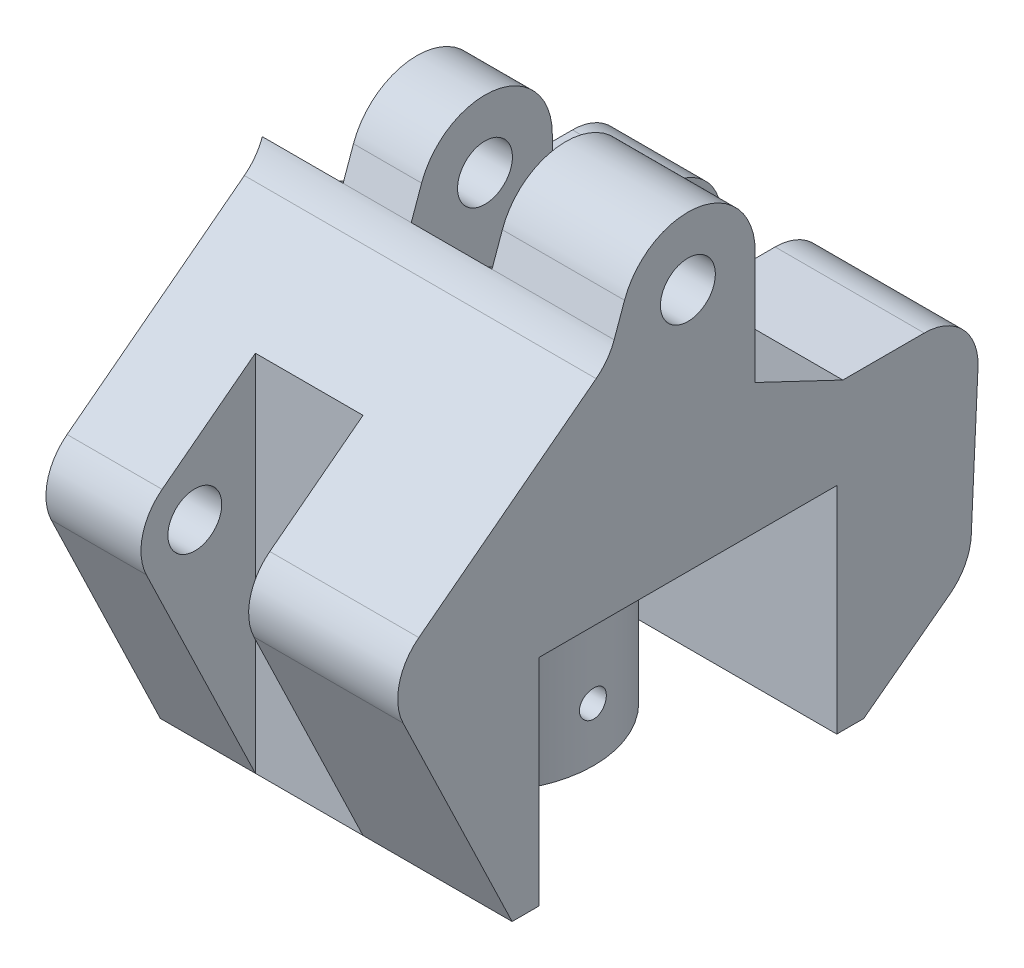
SolidWorks part; units mm, degrees
ref_plane "Front Plane" through (0, 0, 0) normal (0, 0, 1) x (1, 0, 0)
ref_plane "Top Plane" through (0, 0, 0) normal (0, 1, 0) x (1, 0, 0)
ref_plane "Right Plane" through (0, 0, 0) normal (1, 0, 0) x (0, 0, -1)
sketch "Sketch1" plane through (0, 0, 0) normal (1, 0, 0) x (0, 0, -1)
  line L0 (-7.4758, 2.6677) -> (-17.5641, -25.6032)
  line L2 (-17.5641, -25.6032) -> (-17.5641, -28.7782)
  line L3 (-17.5641, -28.7782) -> (17.5641, -28.7782)
  line L4 (17.5641, -25.6032) -> (17.5641, -28.7782)
  line L5 (7.4758, 2.6677) -> (17.5641, -25.6032)
  circle A2 centre (0, 0) radius 3.2385
  arc A3 (7.4758, 2.6677) -> (-7.4758, 2.6677) centre (0, 0) ccw
  point P7 (0, -28.7782)
  dimension "D1" = 6.477
  dimension "D2" = 7.9375
  dimension "D3" = 35.1282
  dimension "D4" = 28.7782
  dimension "D5" = 3.175
extrude "Boss-Extrude1" add sketch "Sketch1" along normal mid plane 35.1282
sketch "Sketch2" plane through (0, 0, 0) normal (0, 0, 1) x (1, 0, 0)
  line L0 (17.5641, -25.6032) -> (17.5641, -28.7782) construction
  line L1 (0, 7.9375) -> (9.525, 7.9375)
  line L2 (0, 7.9375) -> (0, -25.6032)
  line L3 (0, -25.6032) -> (9.525, -25.6032)
  line L4 (9.525, 7.9375) -> (9.525, -25.6032)
  line L5 (17.5641, -28.7782) -> (-17.5641, -28.7782) construction
  line L7 (17.5641, 7.9375) -> (-17.5641, 7.9375) construction
  line L8 (-17.5641, 7.9375) -> (-8.0391, 7.9375)
  line L9 (-17.5641, 7.9375) -> (-17.5641, -25.6032)
  line L10 (-17.5641, -25.6032) -> (-8.0391, -25.6032)
  line L11 (-8.0391, 7.9375) -> (-8.0391, -25.6032)
  dimension "D1" = 3.175
  dimension "D5" = 35.1282
  dimension "D2" = 9.525
  dimension "D3" = 9.525
  dimension "D4" = 8.0391
extrude "Cut-Extrude1" cut sketch "Sketch2" against normal through all both and the other way through all
sketch "Sketch3" plane through (0, -28.7782, 0) normal (0, -1, 0) x (1, 0, 0)
  line L0 (0, -12.827) -> (-12.827, -12.827)
  line L1 (-12.827, -12.827) -> (12.827, -12.827) construction
  line L2 (-12.827, -12.827) -> (-12.827, 12.827) construction
  line L3 (-12.827, 12.827) -> (12.827, 12.827) construction
  line L4 (12.827, -12.827) -> (12.827, 12.827) construction
  line L5 (-12.827, -12.827) -> (12.827, 12.827) construction
  line L6 (-12.827, 12.827) -> (12.827, -12.827) construction
  line L7 (-12.827, -12.827) -> (-12.827, 12.827)
  line L8 (-12.827, 12.827) -> (0, 12.827)
  arc A0 (0, -12.827) -> (0, 12.827) centre (0, 0) ccw
  point P0 (0, 0)
  dimension "D1" = 25.654
extrude "Boss-Extrude2" add sketch "Sketch3" along normal blind 25.4
sketch "Sketch17" plane through (0, -54.1782, 0) normal (0, -1, 0) x (1, 0, 0)
  circle A0 centre (0, 0) radius 7.9375
  dimension "D1" = 15.875
extrude "Cut-Extrude2" cut sketch "Sketch17" against normal blind 22.225
hole_wizard "1/8 (0.125) Diameter Hole1" positions "Sketch13" profile "Sketch14" hole size "1/8" standard "ANSI Inch" end condition through all
sketch "Sketch13" plane through (-12.827, 0, 0) normal (1, 0, 0) x (0, 0, -1)
  line L0 (0, -47.8282) -> (0, -35.1282) construction
  line L1 (0, -35.1282) -> (0, -28.7782) construction
  line L3 (-12.827, -28.7782) -> (12.827, -28.7782) construction
  point P0 (0, -35.1282)
  point P2 (0, -47.8282)
  dimension "D1" = 6.35
  dimension "D2" = 12.7
sketch "Sketch14" plane through (-12.827, -35.1282, 0) normal (0, 1, 0) x (0, 0, 1)
  line L0 (0, 0) -> (0, 30.3911)
  line L1 (0, 30.3911) -> (1.5875, 30.3911)
  line L2 (1.5875, 30.3911) -> (1.5875, 0)
  line L5 (1.5875, 0) -> (0, 0)
  line L11 (0, -6.35) -> (0, 107.95) construction
  dimension "Thru Hole Dia." = 3.175
  dimension "Thru Hole Depth" = 30.3911
hole_wizard "1/8 (0.125) Diameter Hole3" positions "Sketch15" profile "Sketch16" hole size "1/8" standard "ANSI Inch" end condition through all
sketch "Sketch15" plane through (0, 0, -12.827) normal (0, 0, -1) x (-1, 0, 0)
  line L0 (0, -28.7782) -> (0, -38.3032) construction
  line L1 (-17.5641, -28.7782) -> (17.5641, -28.7782) construction
  line L2 (0, -38.3032) -> (0, -44.6532) construction
  point P0 (0, -38.3032)
  point P2 (0, -44.6532)
  dimension "D1" = 9.525
  dimension "D2" = 6.35
sketch "Sketch16" plane through (0, -38.3032, -12.827) normal (1, 0, 0) x (0, 1, 0)
  line L0 (0, 0) -> (0, 30.3911)
  line L1 (0, 30.3911) -> (1.5875, 30.3911)
  line L2 (1.5875, 30.3911) -> (1.5875, 0)
  line L5 (1.5875, 0) -> (0, 0)
  line L11 (0, -6.35) -> (0, 107.95) construction
  dimension "Thru Hole Dia." = 3.175
  dimension "Thru Hole Depth" = 30.3911
sketch "Sketch18" plane through (-8.0391, 0, 0) normal (-1, 0, 0) x (0, 0, 1)
  line L0 (0, 0) -> (-21.6345, 0) construction
  line L1 (-13.9264, -15.4092) -> (3.4079, -7.1687) construction
  line L2 (0, 0) -> (7.9375, 0) construction
  line L3 (-14.3041, -16.4676) -> (3.7487, -7.8856)
  line L4 (-17.5641, -25.6032) -> (-7.4758, 2.6677) construction
  line L5 (-17.5641, -25.6032) -> (17.5641, -25.6032) construction
  line L6 (-21.6345, 0) -> (-21.6344, -17.5641) construction
  line L7 (-17.5641, -25.6032) -> (-14.3041, -16.4676)
  line L8 (-17.5641, -25.6032) -> (17.5641, -25.6032)
  line L9 (8.6983, -0.7581) -> (17.5641, -25.6032)
  line L10 (-13.5856, -16.126) -> (3.7487, -7.8856) construction
  line L11 (7.4758, 2.6677) -> (17.5641, -25.6032) construction
  line L12 (-21.6344, -17.5641) -> (-18.4594, -17.5641) construction
  line L13 (-18.4594, -17.5641) -> (3.4079, -7.1687) construction
  arc A1 (3.4079, -7.1687) -> (7.9375, 0) centre (0, 0) ccw construction
  arc A2 (3.7487, -7.8856) -> (8.6983, -0.7581) centre (0, 0) ccw
  arc A3 (3.7487, -7.8856) -> (8.7312, 0) centre (0, 0) ccw construction
  circle A4 centre (0, 0) radius 3.2385 construction
  dimension "D2" = 17.5641
  dimension "D3" = 21.6345
  dimension "D4" = 3.175
  dimension "D1" = 0.7937
extrude "Boss-Extrude3" add sketch "Sketch18" along normal up to surface (9.525 mm away) up to face at (-17.5641, -27.1907, 0)
extrude "Boss-Extrude4" add sketch "Sketch18<2>" against normal up to surface (17.5641 mm away) from surface up to face at (9.525, 3.2385, 0) starting at face at (0, -3.2385, 0)
sketch "Sketch18<2>" plane through (-8.0391, 0, 0) normal (-1, 0, 0) x (0, 0, 1) same geometry as "Sketch18"
sketch "Sketch19" plane through (-17.5641, 0, 0) normal (-1, 0, 0) x (0, 0, 1)
  line L0 (-17.5641, -28.7782) -> (-17.5641, -54.1782)
  line L1 (-17.5641, -54.1782) -> (-20.7391, -54.1782)
  line L3 (17.5641, -28.7782) -> (17.5641, -54.1782)
  line L4 (17.5641, -54.1782) -> (20.7391, -54.1782)
  line L5 (20.7391, -54.1782) -> (33.604, -27.4629)
  line L6 (20.7391, -54.1782) -> (27.8829, -54.1782) construction
  line L7 (27.8829, -54.1782) -> (27.8829, -24.7079) construction
  line L8 (-20.7391, -54.1782) -> (-27.8829, -54.1782) construction
  line L9 (-27.8829, -54.1782) -> (-27.8829, -24.7079) construction
  line L12 (3.7487, -7.8856) -> (-14.3041, -16.4676) construction
  line L13 (3.7487, -7.8856) -> (-14.3041, -16.4676) construction
  line L14 (-17.5641, -28.7782) -> (17.5641, -28.7782)
  line L15 (-14.3041, -16.4676) -> (-17.5641, -25.6032)
  line L16 (-17.5641, -25.6032) -> (-17.5641, -28.7782)
  line L17 (8.6983, -0.7581) -> (17.5641, -25.6032)
  line L18 (17.5641, -25.6032) -> (17.5641, -28.7782)
  line L19 (-34.2257, -25.0081) -> (-33.432, -41.7784)
  line L20 (-20.7391, -54.1782) -> (-30.8991, -46.5582)
  line L21 (-14.3041, -16.4676) -> (-18.2804, -18.3579)
  line L22 (-18.2804, -18.3579) -> (-27.8828, -18.3579)
  line L23 (-14.6449, -15.7507) -> (-18.4595, -17.5641) construction
  line L24 (-18.4595, -17.5641) -> (-27.8828, -17.5641) construction
  line L25 (-27.8828, -17.5641) -> (-27.8829, 0) construction
  line L26 (0, 0) -> (-27.8829, 0) construction
  line L29 (7.4758, 2.6677) -> (8.6983, -0.7581) construction
  line L30 (31.74, -19.6636) -> (10.8217, -3.6683)
  circle A0 centre (27.8829, -24.7079) radius 3.175
  circle A1 centre (-27.8829, -24.7079) radius 3.175
  arc A2 (-27.8828, -18.3579) -> (-34.2257, -25.0081) centre (-27.8829, -24.7079) ccw
  arc A3 (33.604, -27.4629) -> (31.74, -19.6636) centre (27.8829, -24.7079) ccw
  arc A4 (3.7487, -7.8856) -> (8.6983, -0.7581) centre (0, 0) ccw construction
  arc A5 (3.7487, -7.8856) -> (8.6983, -0.7581) centre (0, 0) ccw construction
  circle A6 centre (-27.0891, -41.4782) radius 3.175
  arc A7 (-33.432, -41.7784) -> (-30.8991, -46.5582) centre (-27.0891, -41.4782) ccw
  arc A8 (8.6983, -0.7581) -> (10.8217, -3.6683) centre (14.6789, 1.376) ccw
  point P27 (-17.5641, -41.4782)
  line M14 (17.5641, -28.7782) -> (17.5641, -25.6032)
  line M15 (17.5641, -25.6032) -> (8.6983, -0.7581)
  line M18 (-14.3041, -16.4676) -> (-17.5641, -25.6032)
  line M19 (-17.5641, -25.6032) -> (-17.5641, -28.7782)
  dimension "D1" = 6.35
  dimension "D4" = 12.7
  dimension "D10" = 6.35
  dimension "D2" = 10.3187
  dimension "D3" = 3.175
  dimension "D5" = 25.4
  dimension "D6" = 9.525
  dimension "D7" = 12.7
  dimension "D9" = 17.5641
  dimension "D8" = 0.7937
extrude "Boss-Extrude5" add sketch "Sketch19" against normal up to surface (35.1282 mm away) contours L19 A7 L20 L1 L0 A2 A1 A6 M19 M18 | L5 A3 L3 L4 A0 M15 M14 region at (-17.5641, -28.1423, 22.1422) region at (-17.5641, -34.3581, -24.5456) up to face at (17.5641, -16.3596, 0)
sketch "Sketch23" plane through (0, 0, 0) normal (0, 1, 0) x (1, 0, 0)
  line L0 (17.5641, 20.7391) -> (-17.5641, 20.7391) construction
  line L1 (-6.35, 20.7391) -> (6.35, 20.7391)
  line L2 (-6.35, 20.7391) -> (-6.35, 34.7091)
  line L3 (-6.35, 34.7091) -> (6.35, 34.7091)
  line L4 (6.35, 20.7391) -> (6.35, 34.7091)
  line L6 (17.5641, -20.7391) -> (-17.5641, -20.7391) construction
  line L7 (-6.35, -20.7391) -> (6.35, -20.7391)
  line L8 (-6.35, -20.7391) -> (-6.35, -34.2329)
  line L9 (-6.35, -34.2329) -> (6.35, -34.2329)
  line L10 (6.35, -20.7391) -> (6.35, -34.2329)
  line L12 (0, 20.7391) -> (0, -20.7391) construction
  line L16 (-17.5641, -34.2329) -> (17.5641, -34.2329) construction
  dimension "D1" = 12.7
  dimension "D2" = 13.97
extrude "Cut-Extrude4" cut sketch "Sketch23" against normal through all both and the other way through all
sketch "Sketch24" plane through (17.5641, 0, 0) normal (1, 0, 0) x (0, 0, -1)
  circle A0 centre (-27.8829, -24.7079) radius 3.9688
  circle A1 centre (27.8829, -24.7079) radius 3.9687
  circle A2 centre (-27.8829, -24.7079) radius 3.175 construction
  dimension "D1" = 0.7937
extrude "Cut-Extrude5" [suppressed] cut sketch "Sketch24" against normal up to surface (12.7 mm away) from surface
sketch "Sketch25" [suppressed] plane through (-17.5641, 0, 0) normal (-1, 0, 0) x (0, 0, 1)
  line L0 (-20.7391, -22.3266) -> (-19.3229, -18.3579)
  line L2 (-19.3229, -18.3579) -> (-20.7391, -18.3579)
  line L3 (-20.7391, -18.3579) -> (-20.7391, -22.3266)
  line L4 (-14.3041, -16.4676) -> (-7.4758, 2.6677) construction
  line L5 (-18.2804, -18.3579) -> (-27.8828, -18.3579) construction
extrude "Cut-Extrude6" [suppressed] cut sketch "Sketch25" against normal up to surface (12.7 mm away) from surface
sketch "Sketch22" plane through (-17.5641, 0, 0) normal (-1, 0, 0) x (0, 0, 1)
  line L0 (-7.9375, 0) -> (-7.9375, -13.441)
  line L1 (3.7487, -7.8856) -> (-14.3041, -16.4676) construction
  line L2 (-7.9375, -13.441) -> (-14.3041, -16.4676)
  line L3 (-14.3041, -16.4676) -> (-7.4758, 2.6677)
  arc A0 (-7.4758, 2.6677) -> (-7.9375, 0) centre (0, 0) ccw
  arc A1 (7.4758, 2.6677) -> (-7.4758, 2.6677) centre (0, 0) ccw construction
extrude "Cut-Extrude3" cut sketch "Sketch22" against normal through all
ref_plane "Plane1" through (16.002, 0, 0) normal (-1, 0, 0) x (0, 0, 1)
sketch "Sketch26" plane through (17.5641, 0, 0) normal (1, 0, 0) x (0, 0, -1)
  line L12 (7.9375, -13.441) -> (7.9375, 0)
  line L14 (7.9375, -13.441) -> (7.9375, 0)
  line L16 (-33.604, -27.4629) -> (-20.7391, -54.1782)
  line L17 (-20.7391, -54.1782) -> (-17.5641, -54.1782)
  line L18 (-17.5641, -54.1782) -> (-17.5641, -28.7782)
  line L19 (-17.5641, -28.7782) -> (17.5641, -28.7782)
  line L20 (17.5641, -28.7782) -> (17.5641, -54.1782)
  line L21 (17.5641, -54.1782) -> (20.7391, -54.1782)
  line L22 (20.7391, -54.1782) -> (30.8991, -46.5582)
  line L23 (33.432, -41.7784) -> (34.2257, -25.0081)
  line L24 (18.2804, -18.3579) -> (7.9375, -13.441)
  line L29 (-33.604, -27.4629) -> (-20.7391, -54.1782)
  line L30 (-20.7391, -54.1782) -> (-17.5641, -54.1782)
  line L31 (-17.5641, -54.1782) -> (-17.5641, -28.7782)
  line L32 (-17.5641, -28.7782) -> (17.5641, -28.7782)
  line L33 (17.5641, -28.7782) -> (17.5641, -54.1782)
  line L34 (17.5641, -54.1782) -> (20.7391, -54.1782)
  line L35 (20.7391, -54.1782) -> (30.8991, -46.5582)
  line L36 (33.432, -41.7784) -> (34.2257, -25.0081)
  line L40 (18.2804, -18.3579) -> (7.9375, -13.441)
  line L41 (-7.4758, 2.6677) -> (-8.6983, -0.7581)
  line L42 (-7.4758, 2.6677) -> (-8.6983, -0.7581)
  line L44 (27.8828, -18.3579) -> (18.2804, -18.3579)
  line L45 (27.8828, -18.3579) -> (18.2804, -18.3579)
  line L48 (-10.8217, -3.6683) -> (-31.74, -19.6636)
  line L49 (-10.8217, -3.6683) -> (-31.74, -19.6636)
  circle A0 centre (0, 0) radius 3.2385 construction
  circle A1 centre (0, 0) radius 3.2385
  arc A4 (7.9375, 0) -> (-7.4758, 2.6677) centre (0, 0) ccw
  arc A5 (-31.74, -19.6636) -> (-33.604, -27.4629) centre (-27.8829, -24.7079) ccw
  arc A6 (30.8991, -46.5582) -> (33.432, -41.7784) centre (27.0891, -41.4782) ccw
  arc A7 (34.2257, -25.0081) -> (27.8828, -18.3579) centre (27.8829, -24.7079) ccw
  arc A8 (7.9375, 0) -> (-7.4758, 2.6677) centre (0, 0) ccw
  arc A9 (-31.74, -19.6636) -> (-33.604, -27.4629) centre (-27.8829, -24.7079) ccw
  arc A10 (30.8991, -46.5582) -> (33.432, -41.7784) centre (27.0891, -41.4782) ccw
  arc A11 (34.2257, -25.0081) -> (27.8828, -18.3579) centre (27.8829, -24.7079) ccw
  arc A15 (-10.8217, -3.6683) -> (-8.6983, -0.7581) centre (-14.6789, 1.376) ccw
  arc A16 (-10.8217, -3.6683) -> (-8.6983, -0.7581) centre (-14.6789, 1.376) ccw
  dimension "D1" = 0
extrude "Boss-Extrude6" add sketch "Sketch26" along normal blind 6.3754
sketch "Sketch27" [suppressed] plane through (16.002, 0, 0) normal (-1, 0, 0) x (0, 0, 1)
  line L3 (-20.7391, -54.1782) -> (-30.8991, -46.5582)
  line L4 (-33.3283, -40.297) -> (-30.1533, -23.5266)
  line L5 (-20.7391, -54.1782) -> (-20.7391, -27.0891) construction
  line L6 (-20.7391, -22.3266) -> (-19.3229, -18.3579) construction
  line L8 (-20.7391, -54.1782) -> (-20.7391, -27.0891)
  line L9 (-20.7391, -22.3266) -> (-19.3229, -18.3579)
  line L10 (-19.3229, -18.3579) -> (-23.9141, -18.3579)
  circle A0 centre (-27.0891, -41.4782) radius 6.35 construction
  arc A1 (-33.3283, -40.297) -> (-30.8991, -46.5582) centre (-27.0891, -41.4782) ccw construction
  arc A2 (-30.8991, -46.5582) -> (-33.3283, -40.297) centre (-27.0891, -41.4782) cw
  arc A6 (-20.7391, -27.0891) -> (-20.7391, -22.3266) centre (-23.9141, -24.7079) ccw construction
  arc A7 (-23.9141, -18.3579) -> (-30.1533, -23.5266) centre (-23.9141, -24.7079) ccw construction
  arc A8 (-20.7391, -27.0891) -> (-20.7391, -22.3266) centre (-23.9141, -24.7079) ccw
  arc A9 (-23.9141, -18.3579) -> (-30.1533, -23.5266) centre (-23.9141, -24.7079) ccw
extrude "Cut-Extrude7" [suppressed] cut sketch "Sketch27" against normal blind 3.175
equation "\"D3@Sketch2\"=\"D2@Sketch2\""
equation "\"D2@Sketch18\"=1.383/2"
equation "\"D3@Sketch18\"=0.85175000"
equation "\"D9@Sketch19\"=1.383/2"
